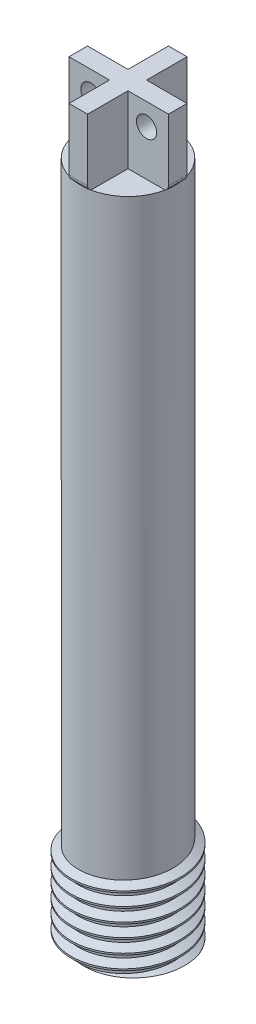
SolidWorks part; units mm, degrees
ref_plane "Front Plane" through (0, 0, 0) normal (0, 0, 1) x (1, 0, 0)
ref_plane "Top Plane" through (0, 0, 0) normal (0, 1, 0) x (1, 0, 0)
ref_plane "Right Plane" through (0, 0, 0) normal (1, 0, 0) x (0, 0, -1)
sketch "Sketch1" plane through (0, 0, 0) normal (0, 1, 0) x (1, 0, 0)
  circle A0 centre (0, 0) radius 7
  dimension "D1" = 14
extrude "Boss-Extrude1" add sketch "Sketch1" along normal blind 100 contours A0
sketch "Sketch4" plane through (0, 0, 0) normal (0, 0, 1) x (1, 0, 0)
  line L0 (0, 0) -> (0, 110) construction
  dimension "D1" = 110
sketch "Sketch5" plane through (0, 0, 0) normal (0, -1, 0) x (1, 0, 0)
  circle A0 centre (0, 0) radius 5.5
  dimension "D1" = 11
extrude "Cut-Extrude2" cut sketch "Sketch5" against normal blind 98
sketch "Sketch9" plane through (0, 0, 0) normal (0, 0, 1) x (1, 0, 0)
  line L0 (0, 0) -> (0, -10) construction
  dimension "D1" = 10
ref_plane "Plane5" through (0, 50, 0) normal (0, 1, 0) x (1, 0, 0)
sketch "Sketch18" plane through (0, 0, 0) normal (0, 0, 1) x (1, 0, 0)
  line L0 (0, 0) -> (0, -5) construction
  dimension "D1" = 5
thread "Thread2" pitch 2 method extrude profile "Thread Profile4" start angle 0, offset 0, length 17, pitch 2, diameter 14
ref_plane "Plane7" through (7, -5, 0) normal (0, 0, 1) x (1, 0, 0)
sketch "Thread Profile4" plane through (7, -5, 0) normal (0, 0, 1) x (1, 0, 0)
  line L0 (0, 0) -> (0, 2) construction
  line L1 (0, 0) -> (1.0825, 0.625)
  line L2 (1.0825, 0.625) -> (1.0825, 0.875)
  line L3 (1.0825, 0.875) -> (0, 1.5)
  line L4 (1.0825, 0.75) -> (0, 0.75) construction
  line L11 (0, 0) -> (0, 1.5)
  point P2 (0, 0)
  dimension "Pitch" = 2
  dimension "Profile_Angle" = 60
  dimension "Profile_Land" = 0.25
  dimension "Profile_Height" = 1.0825
sketch "Sketch22" plane through (0, 0, 0) normal (0, -1, 0) x (1, 0, 0)
  circle A0 centre (0, 0.2255) radius 0.2255
extrude "Cut-Extrude7" cut sketch "Sketch22" along normal blind 10 flip side to cut
sketch "Sketch24" plane through (0, 100, 0) normal (0, 1, 0) x (1, 0, 0)
  line L1 (7.375, 1.375) -> (-7.375, 1.375)
  line L2 (7.375, 1.375) -> (7.375, -1.375)
  line L3 (7.375, -1.375) -> (-7.375, -1.375)
  line L4 (-7.375, 1.375) -> (-7.375, -1.375)
  line L5 (7.375, 1.375) -> (-7.375, -1.375) construction
  line L6 (7.375, -1.375) -> (-7.375, 1.375) construction
  line L7 (1.375, 7.375) -> (-1.375, 7.375)
  line L8 (1.375, 7.375) -> (1.375, -7.375)
  line L9 (1.375, -7.375) -> (-1.375, -7.375)
  line L10 (-1.375, 7.375) -> (-1.375, -7.375)
  line L11 (1.375, 7.375) -> (-1.375, -7.375) construction
  line L12 (1.375, -7.375) -> (-1.375, 7.375) construction
  point P0 (0, 0)
  point P6 (0, 0)
  circle M9 centre (0, 0) radius 7
  dimension "D1" = 14.75
  dimension "D2" = 2.75
extrude "Boss-Extrude2" add sketch "Sketch24" along normal blind 10 contours L10 L1 L3 M9 | L3 L10 L8 M9 | L10 L1 L8 M9 | L1 L8 L3 M9 | L7 L10 L8 M9 | L1 L4 L3 M9 | L3 L2 L1 M9 | L1 L10 L3 L8 | L10 L9 L8 M9 region at (7.1629, 100, 0) region at (4.165, 100, 0) region at (0, 100, 0) region at (0, 100, -4.165) region at (0, 100, -7.1629) region at (-4.165, 100, 0) region at (0, 100, 4.165) region at (0, 100, 7.1629) region at (-7.1629, 100, 0)
fillet "Fillet2" radius 1 4 edges at (0, 100, -7.375) (7.375, 100, 0) (-7.375, 100, 0) (0, 100, 7.375)
sketch "Sketch25" plane through (0, 0, 0) normal (0, 0, 1) x (1, 0, 0)
  line L0 (-4.1193, 100) -> (-4.1193, 106.75) construction
  line L1 (-1.375, 100) -> (-6.8636, 100) construction
  circle A0 centre (-4.1193, 106.75) radius 1.5
  dimension "D2" = 3
  dimension "D1" = 6.75
extrude "Cut-Extrude8" cut sketch "Sketch25" against normal through all both and the other way through all contours A0
mirror "Mirror1" about plane through (0, 0, 0) normal (1, 0, 0) of "Cut-Extrude8"
